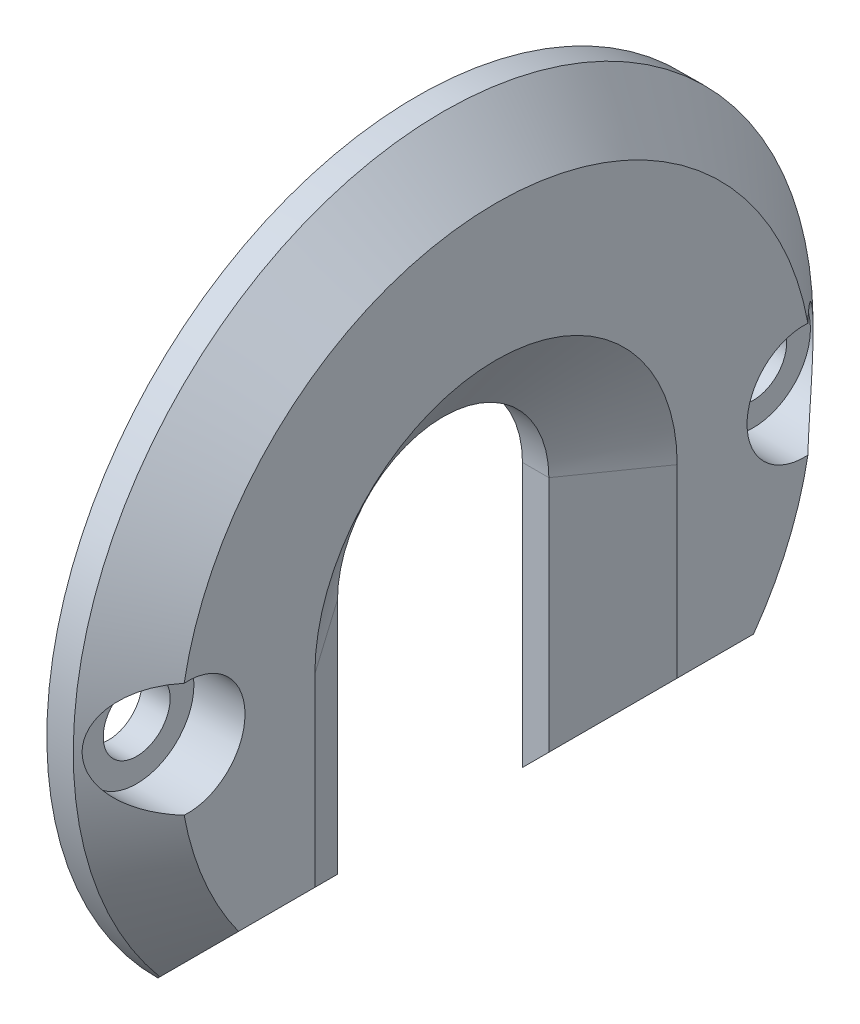
SolidWorks part; units mm, degrees
material "PLA"
ref_plane "Front Plane" through (0, 0, 0) normal (0, 0, 1) x (1, 0, 0)
ref_plane "Top Plane" through (0, 0, 0) normal (0, 1, 0) x (1, 0, 0)
ref_plane "Right Plane" through (0, 0, 0) normal (1, 0, 0) x (0, 0, -1)
sketch "Sketch1" plane through (0, 0, 0) normal (1, 0, 0) x (0, 0, -1)
  line L0 (-6, -10.5) -> (-6, 0)
  line L3 (6, -10.5) -> (6, 0)
  line L4 (6, -10.5) -> (18.1865, -10.5)
  line L5 (-6, -10.5) -> (-18.1865, -10.5)
  arc A0 (18.1865, -10.5) -> (-18.1865, -10.5) centre (0, 0) ccw
  arc A1 (-6, 0) -> (6, 0) centre (0, 0) cw
  point P4 (0, 0)
  dimension "D1" = 42
  dimension "D2" = 12
  dimension "D3" = 10.5
extrude "Boss-Extrude1" add sketch "Sketch1" along normal blind 4.5
sketch "Sketch2" plane through (0, 0, 0) normal (0, 0, 1) x (1, 0, 0)
  line L0 (4.5, -10.5) -> (0, -15)
  line L1 (0, -15) -> (0, -10.5)
  line L2 (0, -10.5) -> (4.5, -10.5)
extrude "Boss-Extrude2" add sketch "Sketch2" against normal up to surface and the other way up to surface up to face at (2.25, 5.25, 0) other way up to face at (2.25, 5.25, 0)
extrude "Cut-Extrude1" cut sketch "Sketch2<2>" against normal up to surface and the other way up to surface contours L0 L1 L2 up to face at (2.25, -5.25, -6) other way up to face at (2.25, -5.25, 6)
sketch "Sketch2<2>" plane through (0, 0, 0) normal (0, 0, 1) x (1, 0, 0) same geometry as "Sketch2"
hole_wizard "CBORE for M3 Hex Socket Head Cap Screw1" positions "Sketch3" profile "Sketch5" counterbore size "M3" standard "ISO"
sketch "Sketch3" plane through (4.5, 0, 0) normal (1, 0, 0) x (0, 0, -1)
  line L0 (17.5, 0) -> (0, 0)
  line L1 (0, 0) -> (-17.5, 0)
  point P0 (-17.5, 0)
  point P2 (17.5, 0)
  dimension "D1" = 35
sketch "Sketch5" plane through (4.5, 0, 17.5) normal (0, 1, 0) x (0, 0, -1)
  line L0 (0, 0) -> (0, 8.1416)
  line L1 (0, 8.1416) -> (1.9, 7)
  line L2 (1.9, 7) -> (1.9, 2.9)
  line L3 (1.9, 2.9) -> (3.25, 2.9)
  line L4 (3.25, 2.9) -> (3.25, 0)
  line L5 (3.25, 0) -> (0, 0)
  line L10 (0, 8.1416) -> (-1.9, 7) construction
  line L11 (0, -6.35) -> (0, 107.95) construction
  dimension "Hole Dia." = 3.8
  dimension "Hole Depth" = 7
  dimension "C'Bore Dia." = 6.5
  dimension "C'Bore Depth" = 2.9
  dimension "Drill Angle" = 118
chamfer "Chamfer1" distance 3 angle 55 3 edges at (4.5, -5.25, 6) (4.5, -5.25, -6) (4.5, 6, 0) first distance on face at (2.25, -6.375, 6) first distance on face at (2.25, -6.375, -6) first distance on face at (2.25, 3, 0)
chamfer "Chamfer2" distance 3 angle 45 1 edges at (4.5, 21, 0)
other "Freeze***"
